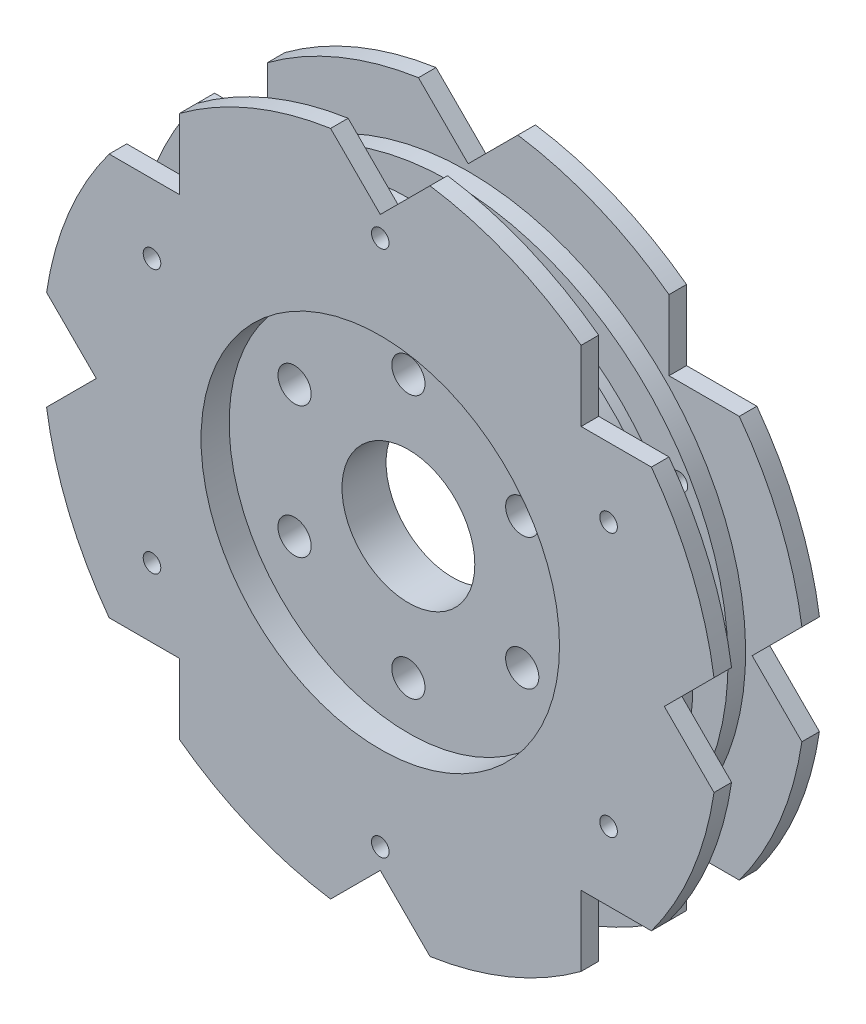
SolidWorks part; units mm, degrees
material "PE High Density Film"
ref_plane "Front Plane" through (0, 0, 0) normal (0, 0, 1) x (1, 0, 0)
ref_plane "Top Plane" through (0, 0, 0) normal (0, 1, 0) x (1, 0, 0)
ref_plane "Right Plane" through (0, 0, 0) normal (1, 0, 0) x (0, 0, -1)
sketch "Sketch1" plane through (0, 0, 0) normal (0, 0, 1) x (1, 0, 0)
  line L0 (0, 0) -> (0, 60.96)
  line L1 (-8.9803, 60.2949) -> (0, 51.3147)
  line L2 (0, 51.3147) -> (8.9803, 60.2949)
  line L3 (36.2849, 48.9849) -> (36.2849, 36.2849)
  line L4 (36.2849, 36.2849) -> (48.9849, 36.2849)
  line L5 (60.2949, 8.9803) -> (51.3147, 0)
  line L6 (51.3147, 0) -> (60.2949, -8.9803)
  line L7 (48.9849, -36.2849) -> (36.2849, -36.2849)
  line L8 (36.2849, -36.2849) -> (36.2849, -48.9849)
  line L9 (8.9803, -60.2949) -> (0, -51.3147)
  line L10 (0, -51.3147) -> (-8.9803, -60.2949)
  line L11 (-36.2849, -48.9849) -> (-36.2849, -36.2849)
  line L12 (-36.2849, -36.2849) -> (-48.9849, -36.2849)
  line L13 (-60.2949, -8.9803) -> (-51.3147, 0)
  line L14 (-51.3147, 0) -> (-60.2949, 8.9803)
  line L15 (-48.9849, 36.2849) -> (-36.2849, 36.2849)
  line L16 (-36.2849, 36.2849) -> (-36.2849, 48.9849)
  arc A0 (-60.2949, -8.9803) -> (-48.9849, -36.2849) centre (0, 0) ccw
  arc A1 (-48.9849, 36.2849) -> (-60.2949, 8.9803) centre (0, 0) ccw
  arc A2 (-36.2849, -48.9849) -> (-8.9803, -60.2949) centre (0, 0) ccw
  arc A3 (8.9803, -60.2949) -> (36.2849, -48.9849) centre (0, 0) ccw
  arc A4 (48.9849, -36.2849) -> (60.2949, -8.9803) centre (0, 0) ccw
  arc A5 (60.2949, 8.9803) -> (48.9849, 36.2849) centre (0, 0) ccw
  arc A6 (36.2849, 48.9849) -> (8.9803, 60.2949) centre (0, 0) ccw
  arc A7 (-8.9803, 60.2949) -> (-36.2849, 48.9849) centre (0, 0) ccw
  point P30 (0, 0)
  dimension "D1" = 121.92
  dimension "D2" = 45
  dimension "D3" = 12.7
  dimension "D4" = 8
extrude "Boss-Extrude1" add sketch "Sketch1" along normal blind 19.05 contours L8 A3 L9 L10 A2 L11 L12 A0 L13 L14 A1 L15 L16 A7 L1 L2 A6 L3 L4 A5 L5 L6 A4 L7
sketch "Sketch2" plane through (0, 0, 19.05) normal (0, 0, 1) x (1, 0, 0)
  circle A0 centre (0, 0) radius 12
  dimension "D1" = 24
extrude "Cut-Extrude1" cut sketch "Sketch2" against normal through all contours A0 region at (0, 0, 19.05)
sketch "Sketch3" plane through (0, 0, 19.05) normal (0, 0, 1) x (1, 0, 0)
  circle A0 centre (0, 0) radius 32.385
  dimension "D1" = 64.77
extrude "Cut-Extrude2" cut sketch "Sketch3" against normal blind 5.08
sketch "Sketch4" plane through (0, 0, 0) normal (0, 0, -1) x (-1, 0, 0)
  circle A0 centre (0, 0) radius 28.4
  dimension "D1" = 56.8
extrude "Cut-Extrude3" cut sketch "Sketch4" against normal blind 6
sketch "Sketch5" plane through (0, 0, 6) normal (0, 0, -1) x (-1, 0, 0)
  line L0 (0, 0) -> (0, 23.75) construction
  circle A0 centre (0, 0) radius 23.75 construction
  circle A1 centre (0, 23.75) radius 2.6
  circle A2 centre (20.5681, 11.875) radius 2.6
  circle A3 centre (20.5681, -11.875) radius 2.6
  circle A4 centre (0, -23.75) radius 2.6
  circle A5 centre (-20.5681, -11.875) radius 2.6
  circle A6 centre (-20.5681, 11.875) radius 2.6
  point P17 (0, 0)
  dimension "D1" = 47.5
  dimension "D2" = 5.2
  dimension "D3" = 6
hole_wizard "Ø6.0mm Dowel Hole1" positions "Sketch6" profile "Sketch8" hole size "Ø6.0" standard "ANSI Metric" end condition through all
sketch "Sketch6" plane through (0, 0, 6) normal (0, 0, -1) x (-1, 0, 0)
  point P0 (0, 23.75)
  point P3 (20.5681, 11.875)
  point P6 (20.5681, -11.875)
  point P9 (0, -23.75)
  point P13 (-20.5681, 11.875)
  point P16 (-20.5681, -11.875)
sketch "Sketch8" plane through (0, 23.75, 6) normal (1, 0, 0) x (0, 1, 0)
  line L0 (0, 0) -> (0, 13.05)
  line L1 (0, 13.05) -> (3, 13.05)
  line L2 (3, 13.05) -> (3, 0)
  line L5 (3, 0) -> (0, 0)
  line L11 (0, -6.35) -> (0, 107.95) construction
  dimension "Thru Hole Dia." = 6
  dimension "Thru Hole Depth" = 13.05
ref_plane "Plane1" through (0, 0, 9.525) normal (0, 0, -1) x (-1, 0, 0)
sketch "Sketch9" plane through (0, 0, 9.525) normal (0, 0, -1) x (-1, 0, 0)
  line L0 (0, 0) -> (23.3284, 56.3197) construction
  line L1 (20.2908, 48.9864) -> (11.4909, 52.6315) construction
  line L2 (17.2533, 41.6531) -> (8.4533, 45.2982)
  line L3 (8.4533, 45.2982) -> (14.5284, 59.9648)
  line L4 (14.5284, 59.9648) -> (32.1283, 52.6746)
  line L5 (32.1283, 52.6746) -> (26.0532, 38.008)
  line L6 (26.0532, 38.008) -> (17.2533, 41.6531)
  arc A0 (36.2849, 48.9849) -> (8.9803, 60.2949) centre (0, 0) ccw construction
  circle A1 centre (20.2908, 48.9864) radius 3.4925
  dimension "D1" = 6.985
  dimension "D2" = 7.9375
  dimension "D3" = 19.05
extrude "Cut-Extrude4" [suppressed] cut sketch "Sketch9" against normal mid plane 11.1125
sketch "Sketch10" [suppressed] plane through (0, 0, 0) normal (0, 0, -1) x (-1, 0, 0)
  circle A0 centre (20.2908, 48.9864) radius 3.4925
  circle A1 centre (20.2908, 48.9864) radius 3.4925 construction
extrude "Cut-Extrude5" [suppressed] cut sketch "Sketch10" against normal through all
sketch "Sketch11" plane through (0, 0, 9.525) normal (0, 0, -1) x (-1, 0, 0)
  line L0 (0, 0) -> (0, 50.8) construction
  line L1 (0, 38.1) -> (-15.875, 38.1)
  line L2 (-15.875, 38.1) -> (-15.875, 63.5)
  line L3 (-15.875, 63.5) -> (15.875, 63.5)
  line L4 (15.875, 63.5) -> (15.875, 38.1)
  line L5 (15.875, 38.1) -> (0, 38.1)
  line L6 (0, 50.8) -> (-15.875, 50.8) construction
  line L7 (0, 0) -> (25.4, 0) construction
  dimension "D1" = 25.4
  dimension "D2" = 90
  dimension "D3" = 31.75
  dimension "D4" = 25.4
  dimension "D5" = 50.8
extrude "Cut-Extrude6" [suppressed] cut sketch "Sketch11" against normal mid plane 11.1125
sketch "Sketch12" plane through (0, 0, 0) normal (1, 0, 0) x (0, 0, -1)
  line L0 (0, 0) -> (-19.05, 0) construction
  line L1 (-9.525, 0) -> (-9.525, 60.2949) construction
  line L2 (-19.05, 60.2949) -> (0, 60.2949) construction
  line L3 (-3.175, 62.8349) -> (-15.875, 62.8349)
  line L4 (-15.875, 62.8349) -> (-15.875, 50.1349)
  line L5 (-15.875, 50.1349) -> (-12.7, 50.1349)
  line L6 (-12.7, 50.1349) -> (-12.7, 43.7849)
  line L7 (-12.7, 43.7849) -> (-6.35, 43.7849)
  line L8 (-6.35, 43.7849) -> (-6.35, 50.1349)
  line L9 (-6.35, 50.1349) -> (-3.175, 50.1349)
  line L10 (-3.175, 50.1349) -> (-3.175, 62.8349)
  point P18 (-9.525, 62.8349)
  point P19 (-9.525, 43.7849)
  dimension "D1" = 2.54
  dimension "D2" = 12.7
  dimension "D3" = 12.7
  dimension "D4" = 6.35
  dimension "D5" = 6.35
revolve "Cut-Revolve1" cut sketch "Sketch12" angle 360 about L0
sketch "Sketch13" plane through (0, 0, 0) normal (0, 0, -1) x (-1, 0, 0)
  circle A0 centre (0, 47.625) radius 1.5875
  circle A1 centre (41.2445, 23.8125) radius 1.5875
  circle A2 centre (41.2445, -23.8125) radius 1.5875
  circle A3 centre (0, -47.625) radius 1.5875
  circle A4 centre (-41.2445, -23.8125) radius 1.5875
  circle A5 centre (-41.2445, 23.8125) radius 1.5875
  circle A6 centre (0, 0) radius 47.625
  point P15 (0, 0)
  dimension "D1" = 3.175
  dimension "D3" = 95.25
  dimension "D2" = 6
hole_wizard "1/8 (0.1250) Dowel Hole1" positions "Sketch14" profile "Sketch15" hole size "1/8" standard "ANSI Inch" end condition through all
sketch "Sketch14" plane through (0, 0, 0) normal (0, 0, -1) x (-1, 0, 0)
  point P0 (-41.2445, 23.8125)
  point P3 (0, 47.625)
  point P6 (41.2445, 23.8125)
  point P9 (41.2445, -23.8125)
  point P12 (0, -47.625)
  point P15 (-41.2445, -23.8125)
sketch "Sketch15" plane through (41.2445, 23.8125, 0) normal (1, 0, 0) x (0, 1, 0)
  line L0 (0, 0) -> (0, 19.05)
  line L1 (0, 19.05) -> (1.5875, 19.05)
  line L2 (1.5875, 19.05) -> (1.5875, 0)
  line L5 (1.5875, 0) -> (0, 0)
  line L11 (0, -6.35) -> (0, 107.95) construction
  dimension "Thru Hole Dia." = 3.175
  dimension "Thru Hole Depth" = 19.05
equation "\"D2@Sketch9\"=0.3125"
